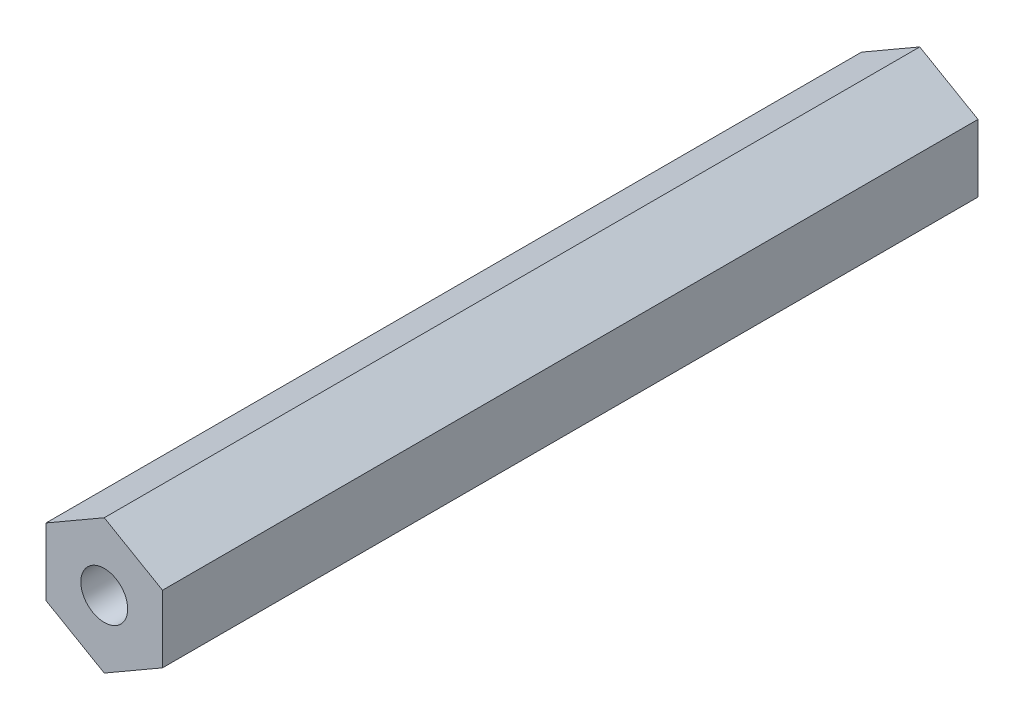
SolidWorks part; units mm, degrees
material "6061-T6 (SS)"
ref_plane "Front Plane" through (0, 0, 0) normal (0, 0, 1) x (1, 0, 0)
ref_plane "Top Plane" through (0, 0, 0) normal (0, 1, 0) x (1, 0, 0)
ref_plane "Right Plane" through (0, 0, 0) normal (1, 0, 0) x (0, 0, -1)
sketch "Sketch1" plane through (0, 0, 0) normal (0, 0, 1) x (1, 0, 0)
  line L1 (6.35, 3.6662) -> (0, 7.3323)
  line L2 (0, 7.3323) -> (-6.35, 3.6662)
  line L3 (-6.35, 3.6662) -> (-6.35, -3.6662)
  line L4 (-6.35, -3.6662) -> (0, -7.3323)
  line L5 (0, -7.3323) -> (6.35, -3.6662)
  line L6 (6.35, -3.6662) -> (6.35, 3.6662)
  circle A0 centre (0, 0) radius 6.35 construction
  point P3 (0, 0)
  point P4 (0, 0)
  point P6 (0, 0)
  point P7 (0, 0)
  point P11 (0, 0)
  point P15 (0, 0)
  point P16 (0, 0)
  dimension ".5" = 12.7
extrude "Boss-Extrude1" add sketch "Sketch1" along normal blind 88.9
hole_wizard "1/4-20 Tapped Hole1" positions "Sketch3" profile "Sketch4" tap size "1/4-20" standard "ANSI Inch"
sketch "Sketch3" plane through (0, 0, 88.9) normal (0, 0, 1) x (1, 0, 0)
  point P0 (0, 0)
sketch "Sketch4" plane through (0, 0, 88.9) normal (1, 0, 0) x (0, -1, 0)
  line L0 (0, 0) -> (0, 18.0438)
  line L1 (0, 18.0438) -> (2.5527, 16.51)
  line L2 (2.5527, 16.51) -> (2.5527, 0)
  line L5 (2.5527, 0) -> (0, 0)
  line L10 (0, 18.0438) -> (-2.5527, 16.51) construction
  line L11 (0, -6.35) -> (0, 107.95) construction
  dimension "Tap Drill Dia." = 5.1054
  dimension "Tap Drill Depth" = 16.51
  dimension "Drill Angle" = 118
cosmetic thread "Hole Thread1" parameters "D1"=12.7, "D2"=6.35
hole_wizard "1/4-20 Tapped Hole2" positions "Sketch6" profile "Sketch5" tap size "1/4-20" standard "ANSI Inch"
sketch "Sketch6" plane through (0, 0, 0) normal (0, 0, -1) x (-1, 0, 0)
  point P0 (0, 0)
sketch "Sketch5" plane through (0, 0, 0) normal (1, 0, 0) x (0, 1, 0)
  line L0 (0, 0) -> (0, 18.0438)
  line L1 (0, 18.0438) -> (2.5527, 16.51)
  line L2 (2.5527, 16.51) -> (2.5527, 0)
  line L5 (2.5527, 0) -> (0, 0)
  line L10 (0, 18.0438) -> (-2.5527, 16.51) construction
  line L11 (0, -6.35) -> (0, 107.95) construction
  dimension "Tap Drill Dia." = 5.1054
  dimension "Tap Drill Depth" = 16.51
  dimension "Drill Angle" = 118
cosmetic thread "Hole Thread2" parameters "D1"=12.7, "D2"=6.35
